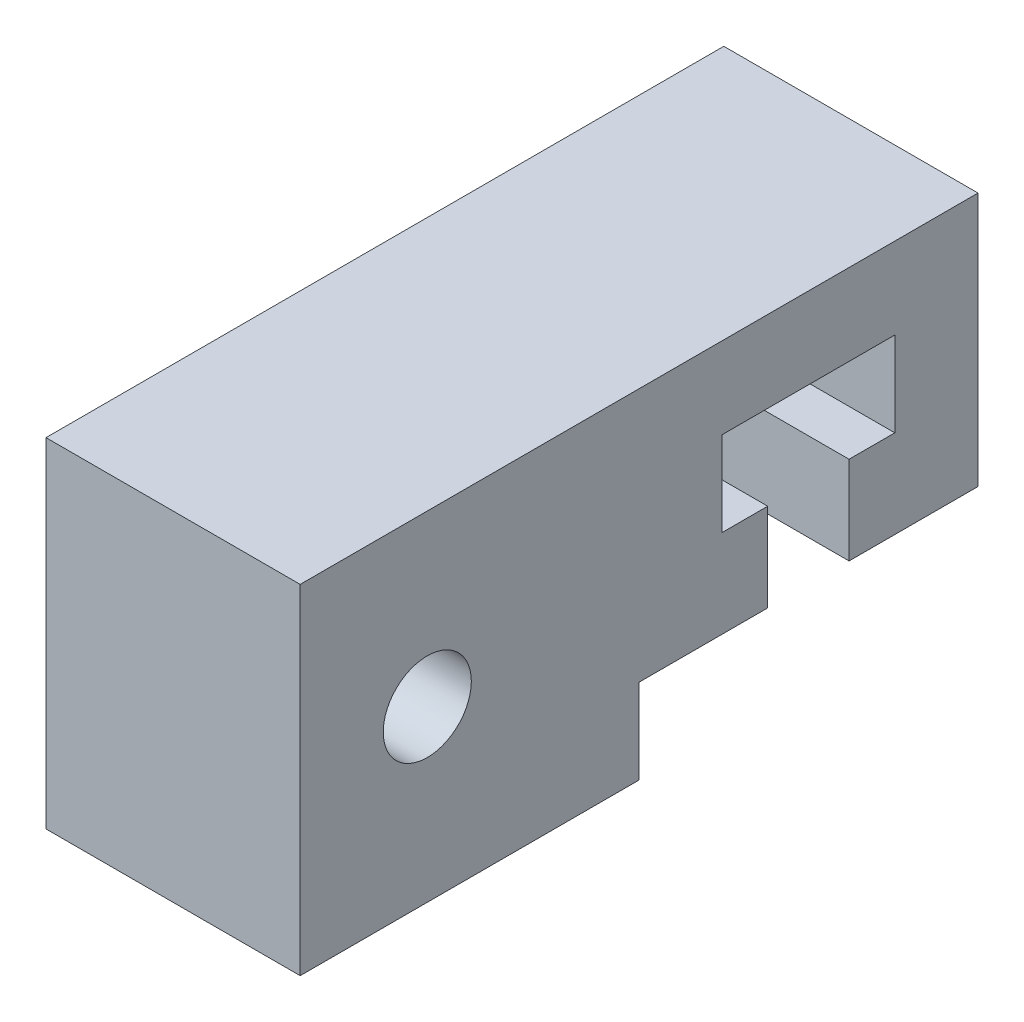
SolidWorks part; units mm, degrees
ref_plane "Front Plane" through (0, 0, 0) normal (0, 0, 1) x (1, 0, 0)
ref_plane "Top Plane" through (0, 0, 0) normal (0, 1, 0) x (1, 0, 0)
ref_plane "Right Plane" through (0, 0, 0) normal (1, 0, 0) x (0, 0, -1)
sketch "Sketch2" plane through (0, 0, 0) normal (1, 0, 0) x (0, 0, -1)
  line L0 (-4.7625, 6.35) -> (-4.7625, -6.35)
  line L1 (-4.7625, -6.35) -> (7.9375, -6.35)
  line L2 (7.9375, -6.35) -> (7.9375, -3.175)
  line L3 (20.6375, -3.175) -> (15.8057, -3.175)
  line L4 (20.6375, -3.175) -> (20.6375, 6.35)
  line L5 (20.6375, 6.35) -> (-4.7625, 6.35)
  line L6 (-19.474, 0) -> (-4.2216, 0) construction
  line L7 (15.8057, -3.175) -> (15.8057, 0.127)
  line L8 (15.8057, 0.127) -> (17.5202, 0.127)
  line L9 (17.5202, 0.127) -> (17.5202, 3.302)
  line L10 (17.5202, 3.302) -> (11.0432, 3.302)
  line L11 (11.0432, 3.302) -> (11.0432, 0.127)
  line L12 (11.0432, 0.127) -> (12.7577, 0.127)
  line L13 (12.7577, 0.127) -> (12.7577, -3.175)
  line L14 (12.7577, -3.175) -> (7.9375, -3.175)
  line L15 (14.2817, 0.9915) -> (14.2817, -22.7495) construction
  circle A0 centre (0, 0) radius 1.651
  point P10 (-4.7625, 0)
  point P21 (14.2817, 3.302)
  dimension "D2" = 3.302
  dimension "D1" = 12.7
  dimension "D3" = 12.7
  dimension "D4" = 9.525
  dimension "D5" = 4.7625
  dimension "D6" = 25.4
  dimension "D7" = 6.477
  dimension "D8" = 3.048
  dimension "D9" = 6.3558
  dimension "D10" = 6.477
  dimension "D11" = 3.175
  dimension "D12" = 3.175
extrude "Boss-Extrude1" add sketch "Sketch2" along normal blind 4.7625 and the other way blind 4.7625
